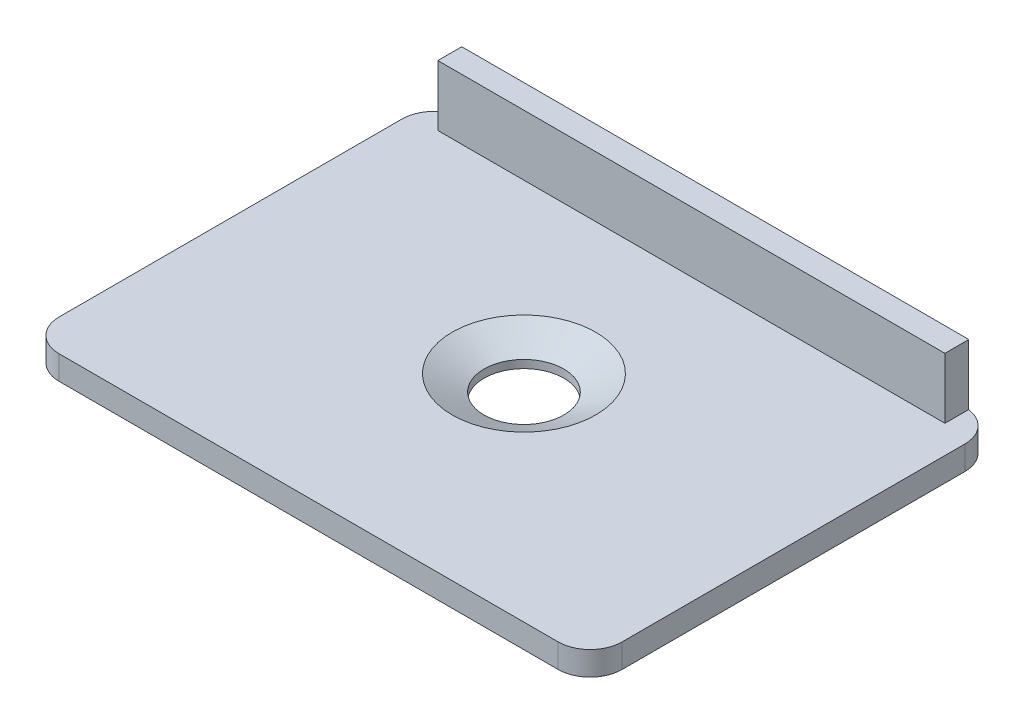
SolidWorks part; units mm, degrees
ref_plane "Front Plane" through (0, 0, 0) normal (0, 0, 1) x (1, 0, 0)
ref_plane "Top Plane" through (0, 0, 0) normal (0, 1, 0) x (1, 0, 0)
ref_plane "Right Plane" through (0, 0, 0) normal (1, 0, 0) x (0, 0, -1)
sketch "Sketch1" plane through (0, 0, 0) normal (0, 1, 0) x (1, 0, 0)
  line L1 (-17.65, 12.75) -> (17.65, 12.75)
  line L2 (-17.65, 12.75) -> (-17.65, -12.75)
  line L3 (-17.65, -12.75) -> (17.65, -12.75)
  line L4 (17.65, 12.75) -> (17.65, -12.75)
  line L5 (-17.65, 12.75) -> (17.65, -12.75) construction
  line L6 (-17.65, -12.75) -> (17.65, 12.75) construction
  point P0 (0, 0)
  dimension "D1" = 35.3
  dimension "D2" = 25.5
extrude "Boss-Extrude1" add sketch "Sketch1" along normal blind 1.5
sketch "Sketch2" plane through (0, 1.5, 0) normal (0, 1, 0) x (1, 0, 0)
  line L0 (17.65, 12.75) -> (-17.65, 12.75) construction
  line L1 (-15.9, 12.75) -> (15.9, 12.75)
  line L2 (-15.9, 12.75) -> (-15.9, 11.25)
  line L3 (-15.9, 11.25) -> (15.9, 11.25)
  line L4 (15.9, 12.75) -> (15.9, 11.25)
  point P6 (0, 11.25)
  dimension "D1" = 0
  dimension "D2" = 31.8
  dimension "D3" = 1.5
extrude "Boss-Extrude2" add sketch "Sketch2" along normal blind 3.8
sketch "Sketch3" plane through (0, 1.5, 0) normal (0, 1, 0) x (1, 0, 0)
  line L0 (-17.65, -12.75) -> (17.65, -12.75) construction
  circle A0 centre (0, 0.75) radius 2.5
  dimension "D1" = 13.5
  dimension "D2" = 5
extrude "Cut-Extrude1" cut sketch "Sketch3" against normal through all both and the other way through all
chamfer "Chamfer1" distance 2 distance2 1 1 edges at (0, 1.5, 1.75) first distance on face at (0, 1.5, 1.75)
fillet "Fillet1" radius 2 4 edges at (17.65, 0.75, -12.75) (-17.65, 0.75, -12.75) (-17.65, 0.75, 12.75) (17.65, 0.75, 12.75)
